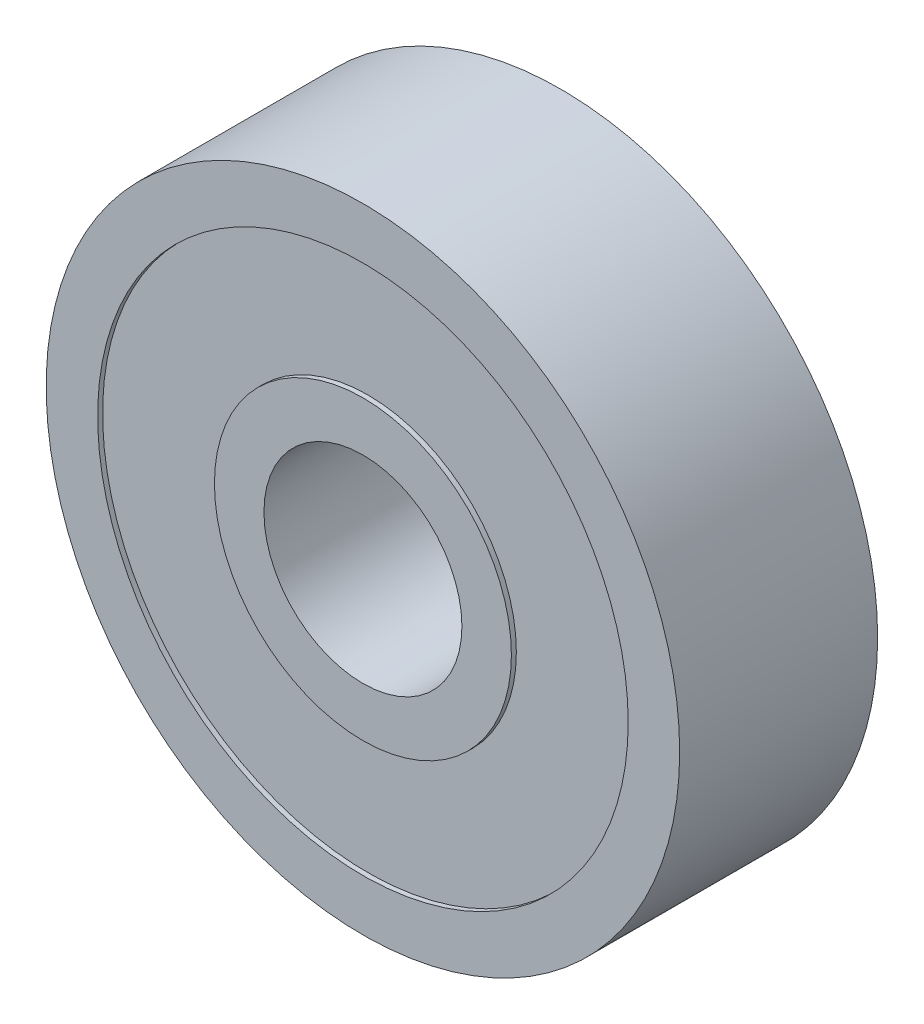
SolidWorks part; units mm, degrees
ref_plane "Front Plane" through (0, 0, 0) normal (0, 0, 1) x (1, 0, 0)
ref_plane "Top Plane" through (0, 0, 0) normal (0, 1, 0) x (1, 0, 0)
ref_plane "Right Plane" through (0, 0, 0) normal (1, 0, 0) x (0, 0, -1)
sketch "Sketch1" plane through (0, 0, 0) normal (0, 0, 1) x (1, 0, 0)
  circle A0 centre (0, 0) radius 2.5
  circle A1 centre (0, 0) radius 8
  circle A2 centre (0, 0) radius 6.7
  circle A3 centre (0, 0) radius 3.75
  dimension "D1" = 16
  dimension "D2" = 5
  dimension "D3" = 13.4
  dimension "D4" = 7.5
extrude "Boss-Extrude1" add sketch "Sketch1" along normal blind 2.5 and the other way blind 2.5 contours A3 A0 | A1 A2 region at (-7.7737, 0, 0) region at (-3.6439, 0, 0)
extrude "Boss-Extrude2" add sketch "Sketch1<3>" along normal blind 2.375 and the other way blind 2.375 contours A2 A3 region at (-6.5105, 0, 0)
sketch "Sketch1<3>" plane through (0, 0, 0) normal (0, 0, 1) x (1, 0, 0) same geometry as "Sketch1"
